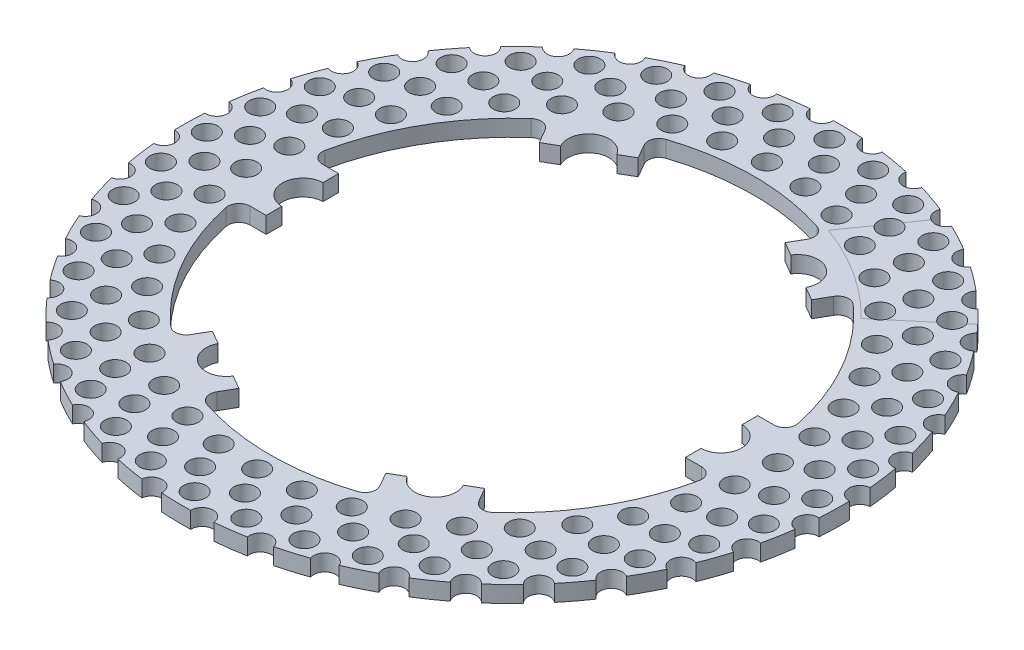
SolidWorks part; units mm, degrees
material "AISI 4130 Steel, annealed at 865C"
ref_plane "Front Plane" through (0, 0, 0) normal (0, 0, 1) x (1, 0, 0)
ref_plane "Top Plane" through (0, 0, 0) normal (0, 1, 0) x (1, 0, 0)
ref_plane "Right Plane" through (0, 0, 0) normal (1, 0, 0) x (0, 0, -1)
sketch "Sketch6" plane through (0, 0, 0) normal (1, 0, 0) x (0, 0, -1)
  line L0 (0, 40.2044) -> (0, -10.3615) construction
ref_axis "Circular Axis" through (0, 40.2044, 0) along (0, -1, 0)
sketch "Sketch1" plane through (0, 0, 0) normal (0, 1, 0) x (1, 0, 0)
  circle A0 centre (0, 0) radius 95.25
  circle A1 centre (0, 0) radius 57.15
  dimension "D1" = 190.5
  dimension "D2" = 38.1
extrude "Boss-Extrude1" add sketch "Sketch1" along normal blind 4.7625
sketch "Sketch2" plane through (0, 4.7625, 0) normal (0, 1, 0) x (1, 0, 0)
  line L0 (0, 0) -> (0, 26.5964) construction
  line L1 (-36.8723, 0) -> (23.1711, 0) construction
  line L2 (-60.4139, 122.8421) -> (-60.4139, 5.9531) construction
  line L3 (-60.5917, 10.4648) -> (-60.5917, 5.9505)
  line L4 (-60.5917, -5.9505) -> (-60.5917, -10.4648)
  line L5 (-60.4139, -5.9531) -> (-60.4139, -123.1247) construction
  line L6 (-60.5917, 10.4648) -> (-52.9717, 10.4648)
  line L7 (-52.9717, 10.4648) -> (-52.9717, -10.4648)
  line L8 (-52.9717, -10.4648) -> (-60.5917, -10.4648)
  arc A1 (-60.5917, 5.9505) -> (-60.5917, -5.9505) centre (-60.4139, 0) ccw
  point P18 (-52.9717, 0)
  dimension "D3" = 11.9062
  dimension "D1" = 60.4139
  dimension "D2" = 245.9668
  dimension "D4" = 0.3556
  dimension "D5" = 20.9296
  dimension "D6" = 7.62
extrude "Hat Area" cut sketch "Sketch2" against normal up to surface (4.7625 mm away) up to face at (0, 0, 95.25)
pattern_circular "CirPattern1" count 6 over 360 about axis through (0, 4.7625, 0) along (0, -1, 0) of "Hat Area"
sketch "Sketch3" plane through (0, 4.7625, 0) normal (0, 1, 0) x (1, 0, 0)
  line L5 (-104.842, 10.4648) -> (-33.181, 10.4648) construction
  line L6 (-61.2132, 85.0948) -> (-27.4543, 26.6227) construction
  line L7 (-39.3586, 47.2416) -> (-37.1546, 43.4241) construction
  line L8 (-69.0616, 10.4648) -> (-18.1256, 10.4648)
  line L9 (-43.5936, 54.5767) -> (-18.1256, 10.4648)
  arc A0 (-69.0616, 10.4648) -> (-43.5936, 54.5767) centre (0, 0) cw
  circle A1 centre (0, 0) radius 95.25 construction
  dimension "D1" = 25.4
extrude "Cut-Extrude2" cut sketch "Sketch3" against normal up to surface (4.7625 mm away) up to face at (0, 0, 0)
pattern_circular "CirPattern2" count 6 over 360 about axis through (0, 4.7625, 0) along (0, -1, 0) of "Cut-Extrude2" reverse direction yes
fillet "Fillet Inner" radius 3.175 12 edges at (-69.0616, 2.3813, 10.4648) (-43.5936, 2.3813, 54.5767) (-25.468, 2.3813, 65.0415) (25.468, 2.3813, 65.0415) (43.5936, 2.3813, 54.5767) (69.0616, 2.3813, 10.4648) (69.0616, 2.3813, -10.4648) (43.5936, 2.3813, -54.5767) (25.468, 2.3813, -65.0415) (-25.468, 2.3813, -65.0415) (-43.5936, 2.3813, -54.5767) (-69.0616, 2.3813, -10.4648)
sketch "Sketch4" plane through (0, 4.7625, 0) normal (0, 1, 0) x (1, 0, 0)
  line L0 (0, 41.5065) -> (0, -16.3205) construction
  line L1 (8.8655, 0) -> (37.2752, 0) construction
  circle A1 centre (0, 0) radius 95.25 construction
  circle A2 centre (-1.5853, 75.2604) radius 3.175
  circle A3 centre (-20.32, 93.0573) radius 3.175
  circle A4 centre (-12.3372, 89.1449) radius 3.175
  circle A5 centre (-5.8611, 83.0546) radius 3.175
  spline S0 degree 2 poles (0, 69.85) (-3.8356, 87.43) (-20.32, 93.0573) knots 0 0 0 1 1 1 construction
  dimension "D5" = 6.35
  dimension "D6" = 8.89
  dimension "D1" = 25.4
  dimension "D2" = 20.32
  dimension "D3" = 8.89
  dimension "D4" = 8.4215
  dimension "D7" = 8.89
  dimension "D8" = 8.89
extrude "Rotor Hole" cut sketch "Sketch4" against normal up to surface (4.7625 mm away) up to face at (0, 0, 0)
pattern_circular "CirPattern3" count 40 over 360 about axis through (0, 4.7625, 0) along (0, -1, 0) of "Rotor Hole" reverse direction yes
sketch "Split Line Sketch" plane through (0, 4.7625, 0) normal (0, 1, 0) x (1, 0, 0)
  line L0 (0, 45.3348) -> (0, -13.9027) construction
  line L1 (15.4882, 42.5534) -> (2.5485, 7.002) construction
  line L2 (24.4113, 67.0696) -> (38.4637, 87.1384)
  line L3 (51.2117, 49.7153) -> (69.5377, 65.0927)
  circle A0 centre (0, 0) radius 71.374 construction
  arc A1 (71.6372, 62.7748) -> (65.6768, 68.9863) centre (0, 0) ccw construction
  arc A2 (48.7325, 81.8395) -> (41.1444, 85.9052) centre (0, 0) ccw construction
  arc A3 (80.5753, 50.7954) -> (75.6601, 57.8629) centre (0, 0) ccw construction
  arc A4 (38.4637, 87.1384) -> (69.5377, 65.0927) centre (0, 0) cw
  arc A5 (24.4113, 67.0696) -> (51.2117, 49.7153) centre (0, 0) cw
  arc A6 (60.935, 73.2085) -> (54.0764, 78.4111) centre (0, 0) ccw construction
  dimension "D2" = 23.876
  dimension "D1" = 20
  dimension "D3" = 15
  dimension "D4" = 15
  dimension "D5" = 38.1
split line "Split Line1"
equation "\"hole_Number\"= 40"
equation "\"D1@CirPattern3\"=\"hole_Number\""
